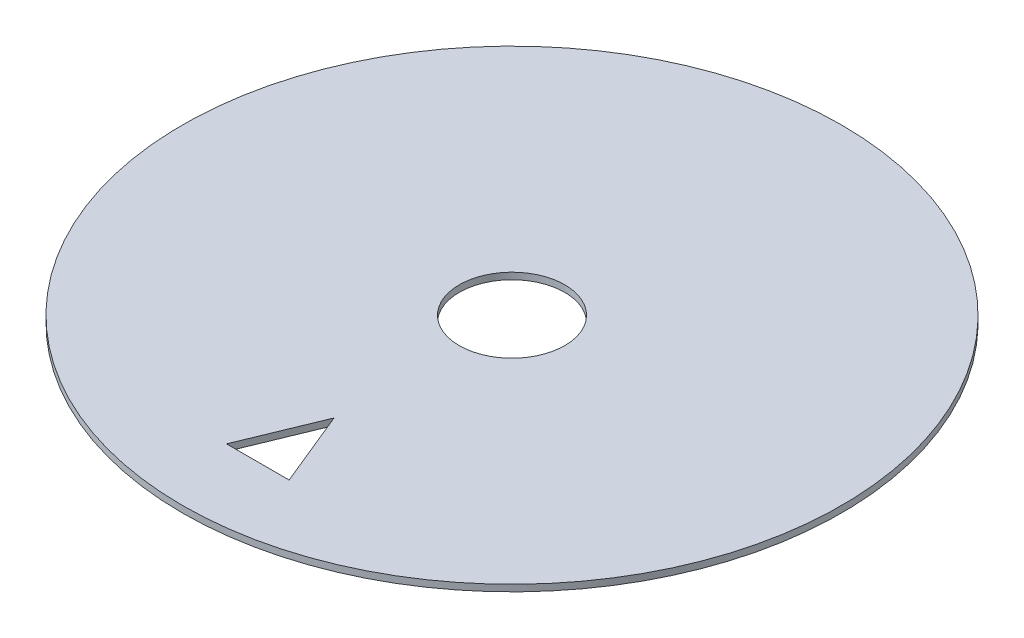
SolidWorks part; units mm, degrees
ref_plane "Front Plane" through (0, 0, 0) normal (0, 0, 1) x (1, 0, 0)
ref_plane "Top Plane" through (0, 0, 0) normal (0, 1, 0) x (1, 0, 0)
ref_plane "Right Plane" through (0, 0, 0) normal (1, 0, 0) x (0, 0, -1)
sketch "Sketch1" plane through (0, 0, 0) normal (0, 1, 0) x (1, 0, 0)
  circle A0 centre (0, 0) radius 100
  dimension "D1" = 200
extrude "Boss-Extrude1" add sketch "Sketch1" along normal blind 2
sketch "Sketch3" plane through (0, 2, 0) normal (0, 1, 0) x (1, 0, 0)
  line L1 (0, -54) -> (-9.5, -77.1247)
  line L3 (-9.5, -77.1247) -> (9.5, -77.1247)
  line L4 (0, 0) -> (0, -100) construction
  line L5 (9.5, -77.1247) -> (0, -54)
  arc A0 (0, -100) -> (69.2521, -72.1398) centre (0, 0) ccw
  circle A1 centre (0, 0) radius 100 construction
  dimension "D4" = 19
  dimension "D1" = 54
  dimension "D2" = 25
  dimension "D3" = 25
extrude "Cut-Extrude1" cut sketch "Sketch3" against normal blind 10 contours L4 L1 L3 | L5 L4 L3 region at (-3.1667, 2, 69.4164) region at (3.1667, 2, 69.4164)
sketch "Sketch5" plane through (0, 2, 0) normal (0, 1, 0) x (1, 0, 0)
  circle A0 centre (0, 0) radius 16
  dimension "D1" = 32
extrude "Cut-Extrude2" cut sketch "Sketch5" against normal up to next
